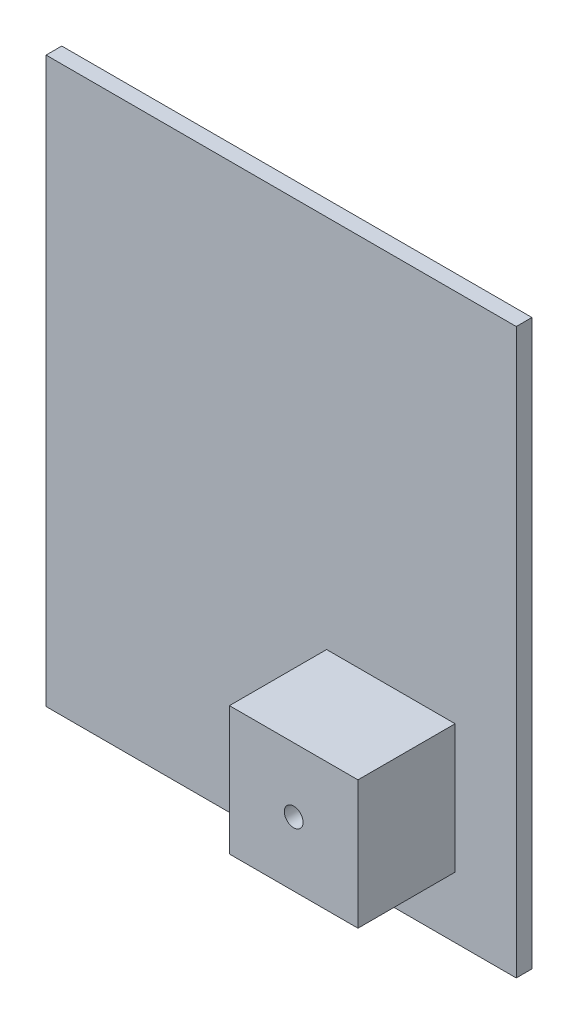
SolidWorks part; units mm, degrees
ref_plane "Front Plane" through (0, 0, 0) normal (0, 0, 1) x (1, 0, 0)
ref_plane "Top Plane" through (0, 0, 0) normal (0, 1, 0) x (1, 0, 0)
ref_plane "Right Plane" through (0, 0, 0) normal (1, 0, 0) x (0, 0, -1)
sketch "Sketch1" plane through (0, 0, 0) normal (0, 0, 1) x (1, 0, 0)
  line L1 (75, -90) -> (-75, -90)
  line L2 (75, -90) -> (75, 90)
  line L3 (75, 90) -> (-75, 90)
  line L4 (-75, -90) -> (-75, 90)
  line L5 (75, -90) -> (-75, 90) construction
  line L6 (75, 90) -> (-75, -90) construction
  line L9 (55.5, -70.5) -> (14.5, -70.5)
  line L10 (55.5, -70.5) -> (55.5, -29.5)
  line L11 (55.5, -29.5) -> (14.5, -29.5)
  line L12 (14.5, -70.5) -> (14.5, -29.5)
  line L13 (55.5, -70.5) -> (14.5, -29.5) construction
  line L14 (55.5, -29.5) -> (14.5, -70.5) construction
  circle A0 centre (35, -50) radius 3
  point P0 (0, 0)
  dimension "D5" = 6
  dimension "D1" = 180
  dimension "D2" = 150
  dimension "D6" = 41
  dimension "D7" = 41
extrude "Boss-Extrude1" add sketch "Sketch1" along normal blind 5 contours L4 L1 L2 L3 L9 L12 L11 L10 region at (-2.3237, 3.3196, 0)
extrude "Boss-Extrude2" add sketch "Sketch1<3>" along normal blind 36 contours L12 L9 L10 L11 A0 region at (35, -69.9202, 0)
sketch "Sketch1<3>" plane through (0, 0, 0) normal (0, 0, 1) x (1, 0, 0) same geometry as "Sketch1"
extrude "Boss-Extrude3" add sketch "Sketch1<5>" against normal blind 20 separate body contours A0 region at (35, -50, 0)
sketch "Sketch1<5>" plane through (0, 0, 0) normal (0, 0, 1) x (1, 0, 0) same geometry as "Sketch1"
